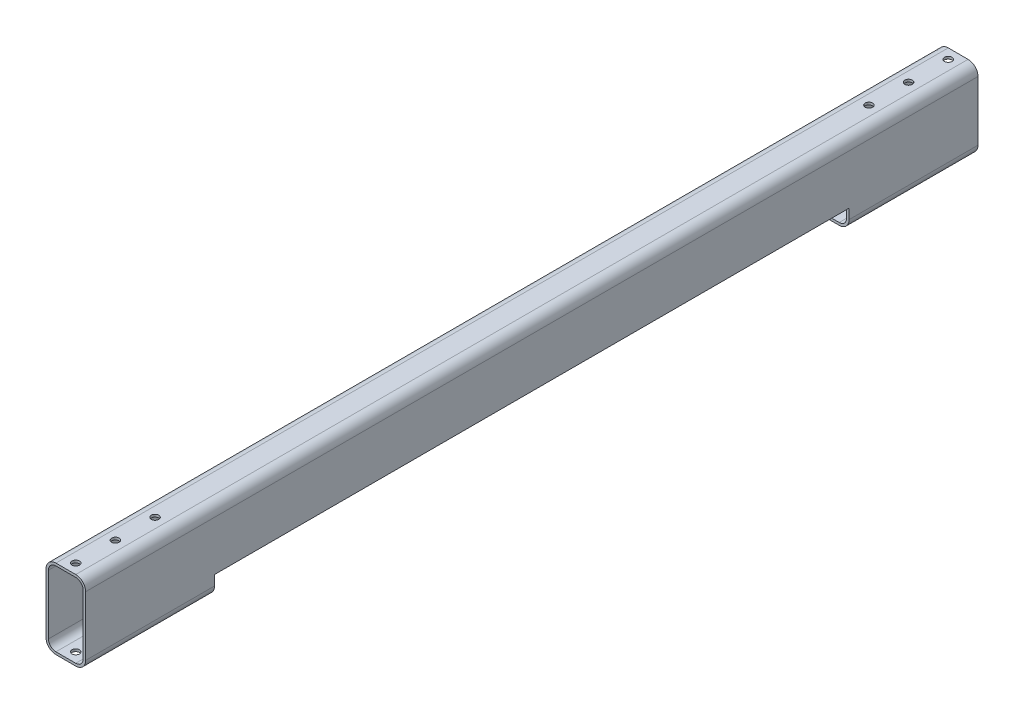
SolidWorks part; units mm, degrees
material "6061-T6 (SS)"
ref_plane "Front Plane" through (0, 0, 0) normal (0, 0, 1) x (1, 0, 0)
ref_plane "Top Plane" through (0, 0, 0) normal (0, 1, 0) x (1, 0, 0)
ref_plane "Right Plane" through (0, 0, 0) normal (1, 0, 0) x (0, 0, -1)
sketch "Sketch1" plane through (0, 0, 0) normal (0, 0, 1) x (1, 0, 0)
  line L1 (-6.35, -25.4) -> (6.35, -25.4)
  line L2 (-12.7, -19.05) -> (-12.7, 19.05)
  line L3 (-6.35, 25.4) -> (6.35, 25.4)
  line L4 (12.7, -19.05) -> (12.7, 19.05)
  line L5 (-12.7, -25.4) -> (12.7, 25.4) construction
  line L6 (-12.7, 25.4) -> (12.7, -25.4) construction
  arc A0 (-12.7, -19.05) -> (-6.35, -25.4) centre (-6.35, -19.05) ccw
  arc A1 (6.35, -25.4) -> (12.7, -19.05) centre (6.35, -19.05) ccw
  arc A2 (6.35, 25.4) -> (12.7, 19.05) centre (6.35, 19.05) cw
  arc A3 (-12.7, 19.05) -> (-6.35, 25.4) centre (-6.35, 19.05) cw
  point P0 (0, 0)
  dimension "D3" = 6.35
  dimension "D1" = 50.8
  dimension "D2" = 25.4
extrude "Extrude-Thin1" add sketch "Sketch1" along normal blind 571.5 thin thin type one direction reverse wall 1.5875
hole_wizard "3/16 (0.1875) Diameter Hole1" positions "3DSketch1" profile "Sketch3" hole size "3/16" standard "ANSI Inch" end condition through all
sketch3d "3DSketch1"
  line L1 (6.35, 25.4, 0) -> (-6.35, 25.4, 0) construction
  line L6 (0, 25.4, 571.5) -> (0, 25.4, 0) construction
  line L7 (6.35, 25.4, 571.5) -> (-6.35, 25.4, 571.5) construction
  point P57 (0, 25.4, 6.35)
  point P59 (0, 25.4, 31.75)
  point P61 (0, 25.4, 57.15)
  point P63 (0, 25.4, 539.75)
  point P65 (0, 25.4, 514.35)
  point P67 (0, 25.4, 565.15)
  dimension "D1" = 25.4
  dimension "D2" = 25.4
  dimension "D3" = 6.35
  dimension "D4" = 25.4
  dimension "D5" = 25.4
  dimension "D6" = 6.35
sketch "Sketch3" plane through (0, 25.4, 565.15) normal (1, 0, 0) x (0, 0, 1)
  line L0 (0, 0) -> (0, 50.8)
  line L1 (0, 50.8) -> (2.3812, 50.8)
  line L2 (2.3812, 50.8) -> (2.3812, 0)
  line L5 (2.3812, 0) -> (0, 0)
  line L11 (0, -6.35) -> (0, 107.95) construction
  dimension "Thru Hole Dia." = 4.7625
  dimension "Thru Hole Depth" = 50.8
sketch "Sketch5" plane through (12.7, 0, 0) normal (1, 0, 0) x (0, 0, -1)
  line L0 (-488.95, -12.7) -> (-488.95, -25.4)
  line L2 (-488.95, -25.4) -> (-82.55, -25.4)
  line L3 (-82.55, -25.4) -> (-82.55, -12.7)
  line L4 (-82.55, -12.7) -> (-488.95, -12.7)
  line L12 (-571.5, -25.4) -> (0, -25.4) construction
  point P11 (-285.75, -25.4)
  point P12 (-285.75, -25.4)
  dimension "D1" = 12.7
  dimension "D2" = 406.4
extrude "Cut-Extrude1" cut sketch "Sketch5" against normal through all
